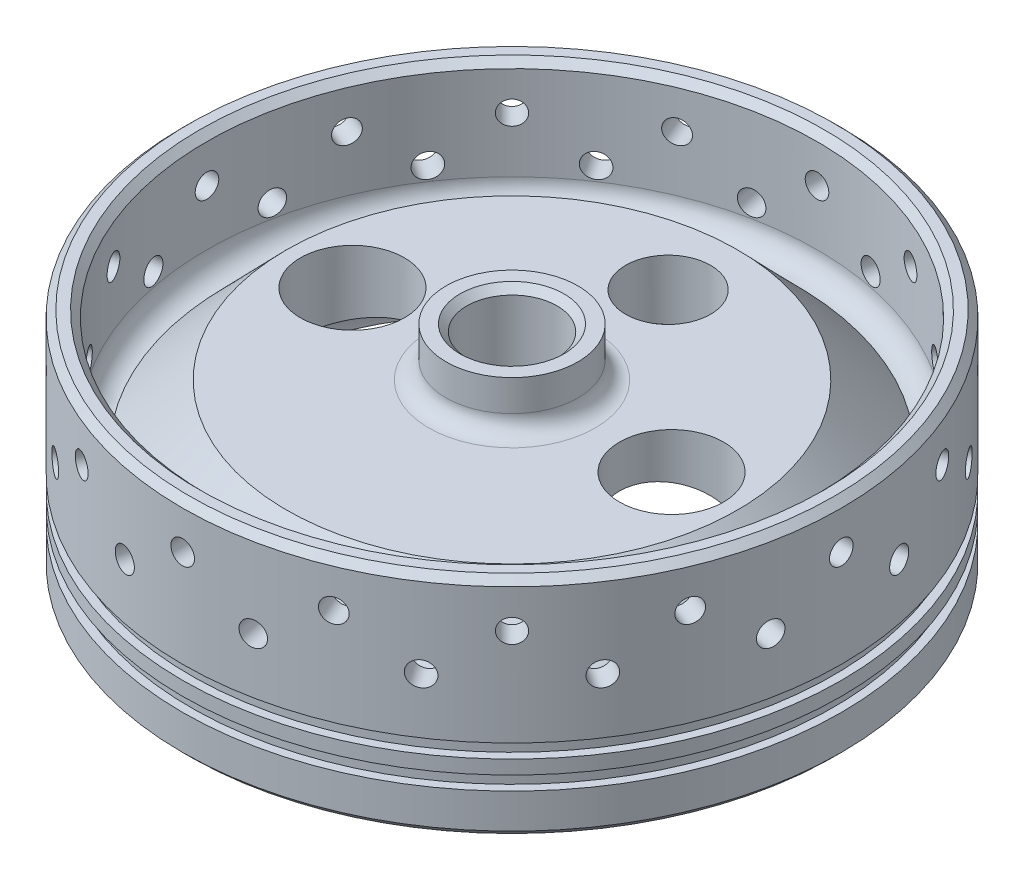
SolidWorks part; units mm, degrees
material "6063-T6"
ref_plane "Płaszczyzna przednia" through (0, 0, 0) normal (0, 0, 1) x (1, 0, 0)
ref_plane "Płaszczyzna górna" through (0, 0, 0) normal (0, 1, 0) x (1, 0, 0)
ref_plane "Płaszczyzna prawa" through (0, 0, 0) normal (1, 0, 0) x (0, 0, -1)
sketch "Sketch1" plane through (0, 0, 0) normal (0, 0, 1) x (1, 0, 0)
  line L0 (0, 47.5) -> (0, 0) construction
  line L1 (0, 0) -> (91, 0) construction
  line L2 (0, 0) -> (0, 37.5) construction
  line L3 (0, 0) -> (-95, 0) construction
  line L4 (91, 0) -> (95, 0)
  line L10 (82, 30) -> (65, 47.5)
  line L13 (88, 65) -> (88, 30)
  line L16 (88, 30) -> (82, 30)
  line L18 (95, 24) -> (92.6, 24)
  line L19 (92.6, 24) -> (92.6, 20)
  line L20 (92.6, 20) -> (95, 20)
  line L21 (95, 16) -> (92.6, 16)
  line L22 (92.6, 16) -> (92.6, 12)
  line L23 (92.6, 12) -> (95, 12)
  line L24 (95, 20) -> (95, 16)
  line L25 (95, 12) -> (95, 0)
  line L28 (95, 65) -> (95, 24)
  line L29 (95, 65) -> (88, 65)
  line L30 (0, 47.5) -> (0, 37.5)
  line L31 (65, 47.5) -> (5.1193, 47.5)
  line L37 (0, 47.5) -> (5.1193, 47.5)
  ellipse E0 centre (0, 0) end of major axis (91, 0) minor radius 37.5 (0, 37.5) -> (91, 0) cw
  dimension "D1" = 91
  dimension "D2" = 37.5
  dimension "D3" = 95
  dimension "D5" = 4
  dimension "D6" = 35
  dimension "D8" = 65
  dimension "D10" = 6
  dimension "D11" = 2.4
  dimension "D12" = 4
  dimension "D13" = 4
  dimension "D14" = 2.4
  dimension "D15" = 4
  dimension "D16" = 12
  dimension "D17" = 10
  dimension "D19" = 7
revolve "Revolve1" add sketch "Sketch1" angle 360 about L0
ref_plane "Plane1" through (0, 0, 95) normal (0, 0, 1) x (1, 0, 0)
ref_plane "Plane2" through (-95, 0, 0) normal (-1, 0, 0) x (0, 0, 1)
sketch "Sketch3" plane through (-95, 0, 0) normal (1, 0, 0) x (0, 0, -1)
  line L0 (95, 65) -> (-95, 65) construction
  point P0 (0, 52)
  dimension "D1" = 13
ref_plane "Płaszczyzna1" through (-18.5336, 0, -93.1746) normal (-0.1951, 0, -0.9808) x (0, 1, 0)
sketch "Szkic2" plane through (-18.5336, 0, -93.1746) normal (-0.1951, 0, -0.9808) x (0, 1, 0)
  line L0 (65, -95) -> (65, 95) construction
  point P0 (40, 0)
  dimension "D1" = 25
hole_wizard "Otwór gwintowany M8x1.252" positions "Sketch6" profile "Sketch7" tap size "M8x1.25" standard "Ansi Metric"
sketch "Sketch6" plane through (-95, 0, 0) normal (1, 0, 0) x (0, 0, -1)
  point P0 (0, 52)
sketch "Sketch7" plane through (-95, 52, 0) normal (0, 1, 0) x (0, 0, 1)
  line L0 (0, 0) -> (0, 17.0429)
  line L1 (0, 17.0429) -> (3.4, 15)
  line L2 (3.4, 15) -> (3.4, 0)
  line L5 (3.4, 0) -> (0, 0)
  line L10 (0, 17.0429) -> (-3.4, 15) construction
  line L11 (0, -6.35) -> (0, 107.95) construction
  dimension "Średnica wiertła gwintu" = 6.8
  dimension "Głębokość otworu gwintowanego" = 15
  dimension "Kąt wiertła" = 118
cosmetic thread "Gwint otworu4" parameters "D1"=2.4, "D2"=8
hole_wizard "Otwór gwintowany M8x1.01" positions "Szkic4" profile "Szkic5" tap size "M8x1.0" standard "Ansi Metric"
sketch "Szkic4" plane through (-18.5336, 0, -93.1746) normal (-0.1951, 0, -0.9808) x (0, 1, 0)
  point P0 (40, 0)
sketch "Szkic5" plane through (-18.5336, 40, -93.1746) normal (0, 1, 0) x (-0.9808, 0, 0.1951)
  line L0 (0, 0) -> (0, 17.103)
  line L1 (0, 17.103) -> (3.5, 15)
  line L2 (3.5, 15) -> (3.5, 0)
  line L5 (3.5, 0) -> (0, 0)
  line L10 (0, 17.103) -> (-3.5, 15) construction
  line L11 (0, -6.35) -> (0, 107.95) construction
  dimension "Średnica wiertła gwintu" = 7
  dimension "Głębokość otworu gwintowanego" = 15
  dimension "Kąt wiertła" = 118
cosmetic thread "Gwint otworu5" parameters "D1"=7.0696, "D2"=8
pattern_circular "CirPattern1" count 16 over 360 about axis through (0, 47.5, 0) along (0, 1, 0) of "Otwór gwintowany M8x1.252", "Otwór gwintowany M8x1.01" reverse direction yes
chamfer "Chamfer2" distance 2 angle 45 1 edges at (-95, 0, 0)
sketch "Sketch8" plane through (0, 47.5, 0) normal (0, 1, 0) x (1, 0, 0)
  circle A0 centre (0, 0) radius 13
  circle A1 centre (-46, 0) radius 15
  circle A2 centre (46, 0) radius 15
  dimension "D1" = 26
  dimension "D2" = 30
  dimension "D5" = 30
  dimension "D3" = 46
  dimension "D4" = 46
extrude "Cut-Extrude1" cut sketch "Sketch8" against normal through all both and the other way through all
fillet "Fillet1" radius 6 1 edges at (-88, 30, 0)
chamfer "Sfazowanie1" distance 2 angle 45 2 edges at (-95, 65, 0) (-88, 65, 0)
sketch "Szkic6" plane through (0, 0, 0) normal (1, 0, 0) x (0, 0, -1)
  line L0 (0, 67.8783) -> (0, 23.2364) construction
  line L1 (-13, 61.5) -> (-13, 31.5)
  line L2 (-13, 61.5) -> (-19, 61.5)
  line L3 (-19, 61.5) -> (-19, 47.5)
  line L7 (-19, 47.5) -> (-19, 31.5)
  line L8 (-19, 31.5) -> (-13, 31.5)
  dimension "D1" = 30
  dimension "D3" = 16
  dimension "D5" = 26
  dimension "D6" = 6
revolve "Obrót1" add sketch "Szkic6" angle 360 about L0
fillet "Zaokrąglenie3" radius 4 1 edges at (-19, 36.6735, 0)
fillet "Zaokrąglenie4" radius 5 1 edges at (19, 47.5, 0)
chamfer "Sfazowanie3" distance 2 angle 45 1 edges at (0, 61.5, 13)
chamfer "Sfazowanie4" distance 2 angle 45 1 edges at (0, 31.5, 13)
sketch "Szkic7" plane through (0, 47.5, 0) normal (0, 1, 0) x (1, 0, 0)
  circle A0 centre (0, 45) radius 12.25
  dimension "D1" = 45
  dimension "D2" = 24.5
extrude "Wytnij-wyciągnięcie1" cut sketch "Szkic7" against normal blind 20
